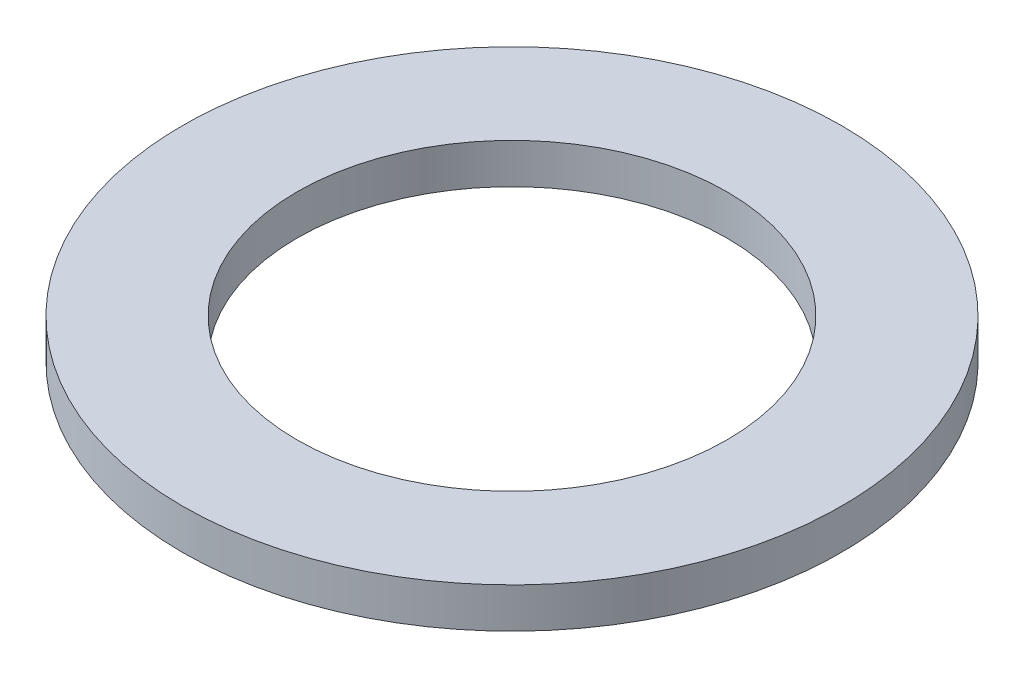
SolidWorks part; units mm, degrees
ref_plane "Front Plane" through (0, 0, 0) normal (0, 0, 1) x (1, 0, 0)
ref_plane "Top Plane" through (0, 0, 0) normal (0, 1, 0) x (1, 0, 0)
ref_plane "Right Plane" through (0, 0, 0) normal (1, 0, 0) x (0, 0, -1)
sketch "Sketch1" plane through (0, 0, 0) normal (0, 1, 0) x (1, 0, 0)
  circle A0 centre (0, 0) radius 57.5
  dimension "FLANGE_OD" = 115
extrude "Boss-Extrude1" add sketch "Sketch1" along normal blind 7
sketch "Sketch2" plane through (0, 0, 0) normal (0, 1, 0) x (1, 0, 0)
  circle A0 centre (0, 0) radius 37.5
  dimension "BORE_D" = 75
extrude "Cut-Extrude1" cut sketch "Sketch2" along normal through all
sketch "Sketch3" plane through (0, 7, 0) normal (0, 1, 0) x (1, 0, 0)
  circle A0 centre (0, 0) radius 22.1115 construction
  circle A1 centre (-22.1115, 0) radius 1.8093
  dimension "BOLT_D" = 3.6186
  dimension "BOLT_PCD" = 44.223
extrude "Cut-Extrude2" cut sketch "Sketch3" against normal blind 5.6659 rebuild error yes
pattern_circular "CirPattern1" count 6 over 360 rebuild error yes
